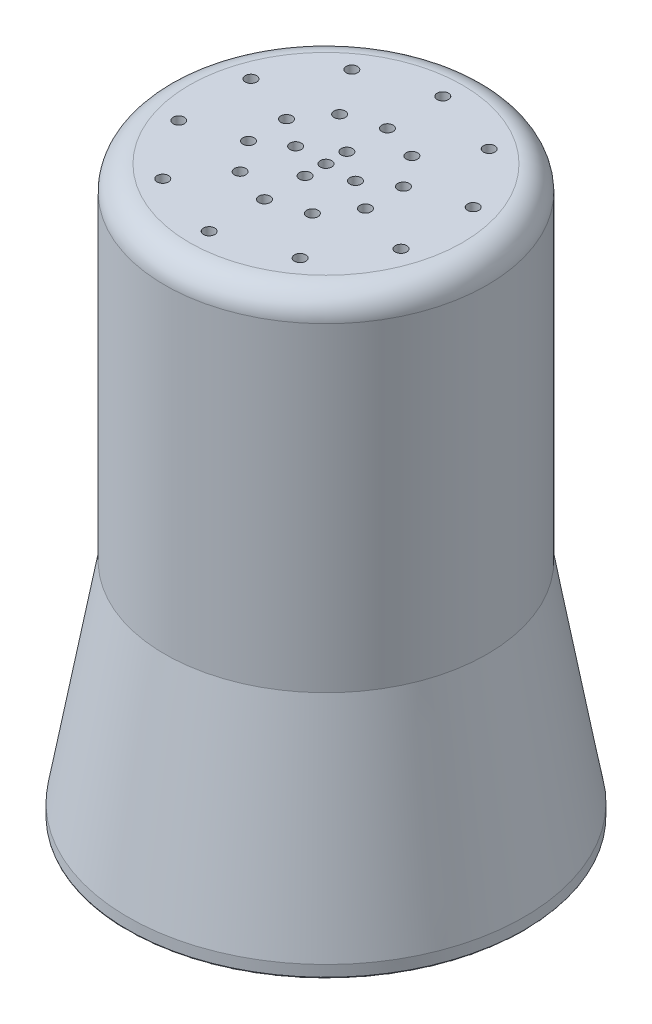
SolidWorks part; units mm, degrees
ref_plane "Front Plane" through (0, 0, 0) normal (0, 0, 1) x (1, 0, 0)
ref_plane "Top Plane" through (0, 0, 0) normal (0, 1, 0) x (1, 0, 0)
ref_plane "Right Plane" through (0, 0, 0) normal (1, 0, 0) x (0, 0, -1)
sketch "Sketch1" plane through (0, 0, 0) normal (0, 0, 1) x (1, 0, 0)
  line L0 (65.5, 90.0692) -> (65.5, 230)
  line L1 (65.5, 230) -> (0, 230)
  line L7 (62.5, 0) -> (62.5, 220)
  line L8 (62.5, 220) -> (-0.5, 220)
  line L10 (-0.5, 220) -> (0, 220)
  line L13 (80.5, 5) -> (80.5, 0)
  line L14 (80.5, 0) -> (62.5, 0)
  line L15 (0, 230) -> (0, 220)
  line L16 (65.5, 90.0692) -> (80.5, 5)
  dimension "D1" = 3
  dimension "D2" = 10
  dimension "D6" = 62.5
  dimension "D3" = 5
  dimension "D4" = 18
  dimension "D5" = 230
  dimension "D7" = 80
revolve "Revolve1" add sketch "Sketch1" angle 360 about L15 region at (70.6002, 47.1115, 0)
sketch "Sketch2" plane through (0, 0, 0) normal (0, -1, 0) x (1, 0, 0)
  circle A0 centre (0, 0) radius 80.5 construction
  circle A1 centre (0, 0) radius 62.5 construction
  circle A2 centre (0, 0) radius 80.5 construction
  circle A3 centre (0, 0) radius 62.5 construction
  circle A4 centre (0, 0) radius 73 construction
  circle A5 centre (73, 0) radius 2.3
  circle A6 centre (67.4432, -27.9359) radius 2.3
  circle A7 centre (51.6188, -51.6188) radius 2.3
  circle A8 centre (27.9359, -67.4432) radius 2.3
  circle A9 centre (0, -73) radius 2.3
  circle A10 centre (-27.9359, -67.4432) radius 2.3
  circle A11 centre (-51.6188, -51.6188) radius 2.3
  circle A12 centre (-67.4432, -27.9359) radius 2.3
  circle A13 centre (-73, 0) radius 2.3
  circle A14 centre (-67.4432, 27.9359) radius 2.3
  circle A15 centre (-51.6188, 51.6188) radius 2.3
  circle A16 centre (-27.9359, 67.4432) radius 2.3
  circle A17 centre (0, 73) radius 2.3
  circle A18 centre (27.9359, 67.4432) radius 2.3
  circle A19 centre (51.6188, 51.6188) radius 2.3
  circle A20 centre (67.4432, 27.9359) radius 2.3
  point P42 (0, 0)
  dimension "D1" = 161
  dimension "D2" = 125
  dimension "D3" = 146
  dimension "D4" = 4.6
  dimension "D5" = 16
extrude "Cut-Extrude1" cut sketch "Sketch2" against normal blind 10
sketch "Sketch4" plane through (0, 230, 0) normal (0, 1, 0) x (1, 0, 0)
  circle A0 centre (0, 0) radius 25 construction
  circle A1 centre (0, 0) radius 47.5 construction
  circle A2 centre (0, 47.5) radius 2.3
  circle A3 centre (0, 25) radius 2.3
  circle A4 centre (27.9198, 38.4283) radius 2.3
  circle A5 centre (14.6946, 20.2254) radius 2.3
  circle A6 centre (45.1752, 14.6783) radius 2.3
  circle A7 centre (23.7764, 7.7254) radius 2.3
  circle A8 centre (45.1752, -14.6783) radius 2.3
  circle A9 centre (23.7764, -7.7254) radius 2.3
  circle A10 centre (27.9198, -38.4283) radius 2.3
  circle A11 centre (14.6946, -20.2254) radius 2.3
  circle A12 centre (0, -47.5) radius 2.3
  circle A13 centre (0, -25) radius 2.3
  circle A14 centre (-27.9198, -38.4283) radius 2.3
  circle A15 centre (-14.6946, -20.2254) radius 2.3
  circle A16 centre (-45.1752, -14.6783) radius 2.3
  circle A17 centre (-23.7764, -7.7254) radius 2.3
  circle A18 centre (-45.1752, 14.6783) radius 2.3
  circle A19 centre (-23.7764, 7.7254) radius 2.3
  circle A20 centre (-27.9198, 38.4283) radius 2.3
  circle A21 centre (-14.6946, 20.2254) radius 2.3
  circle A22 centre (0, 0) radius 2.3
  circle A23 centre (11.9975, 0) radius 2.3
  circle A24 centre (-12.3415, 0) radius 2.3
  circle A25 centre (0, 8.5) radius 2.3
  circle A26 centre (0, -8.5) radius 2.3
  point P47 (0, 0)
  dimension "D1" = 50
  dimension "D2" = 95
  dimension "D3" = 4.6
  dimension "D4" = 10
  dimension "D5" = 8.5
  dimension "D6" = 8.5
extrude "Cut-Extrude2" cut sketch "Sketch4" against normal blind 6.25
chamfer "Chamfer2" [suppressed] distance 1.5 angle 45
chamfer "Chamfer3" distance 20 angle 45 1 edges at (-62.5, 220, 0)
fillet "Fillet10" radius 10 1 edges at (-65.5, 230, 0)
fillet "Fillet15" radius 0.5 1 edges at (-80.5, 0, 0)
sketch "Sketch6" plane through (0, 0, 0) normal (0, -1, 0) x (1, 0, 0)
  line L1 (-0.5, 67.5) -> (0.5, 67.5)
  line L2 (-0.5, 67.5) -> (-0.5, 64.5)
  line L3 (-0.5, 64.5) -> (0.5, 64.5)
  line L4 (0.5, 67.5) -> (0.5, 64.5)
  line L5 (-0.5, 67.5) -> (0.5, 64.5) construction
  line L6 (-0.5, 64.5) -> (0.5, 67.5) construction
  circle A0 centre (0, 0) radius 66 construction
  point P3 (0, 66)
  dimension "D3" = 132
  dimension "D1" = 3
  dimension "D2" = 1
ref_axis "Axis1" [suppressed] through (0, 280.7413, 0) along (0, -1, 0)
equation "\"ChamberRAD\"= 125 / 2"
equation "\"D6@Sketch1\"=\"ChamberRAD\""
equation "\"ChamberHeight\"= 230"
equation "\"D5@Sketch1\"=\"ChamberHeight\""
equation "\"D3@Sketch2\"=(\"D2@Sketch2\"+\"D1@Sketch2\")/2+3"
